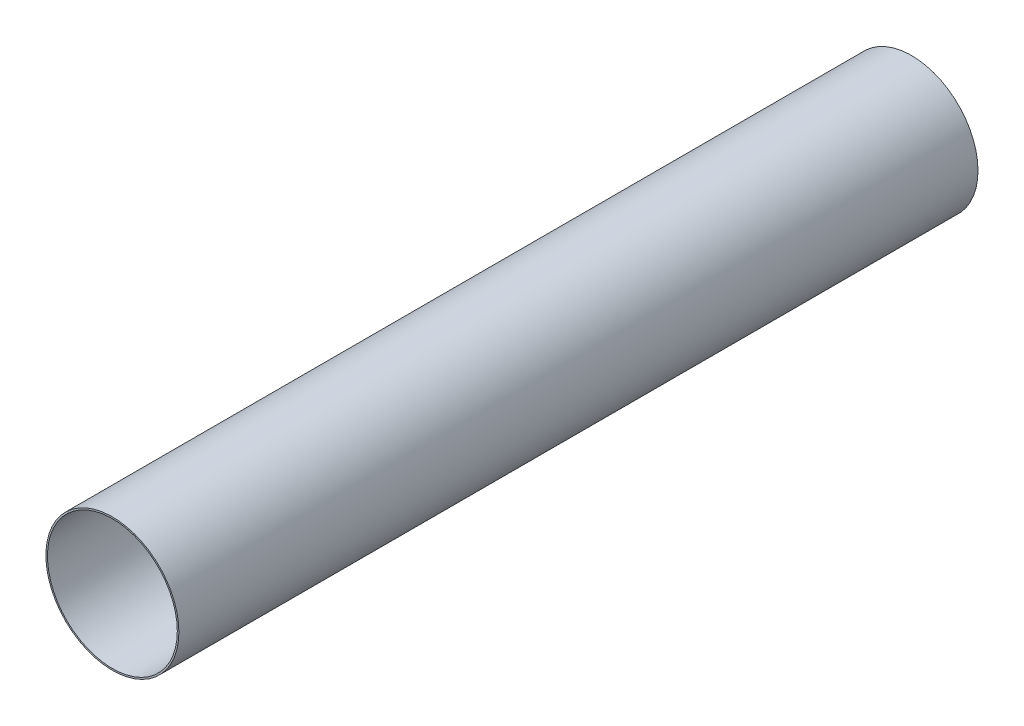
SolidWorks part; units mm, degrees
material "Thornel Mat VMA"
ref_plane "Front Plane" through (0, 0, 0) normal (0, 0, 1) x (1, 0, 0)
ref_plane "Top Plane" through (0, 0, 0) normal (0, 1, 0) x (1, 0, 0)
ref_plane "Right Plane" through (0, 0, 0) normal (1, 0, 0) x (0, 0, -1)
sketch "Sketch1" plane through (0, 0, 0) normal (0, 0, 1) x (1, 0, 0)
  circle A0 centre (0, 0) radius 84.55
  circle A1 centre (0, 0) radius 82.55
  dimension "D1" = 165.1
  dimension "D2" = 169.1
extrude "Boss-Extrude1" add sketch "Sketch1" along normal mid plane 1016
equation "\"TubeDiameter\"= 6.500in"
equation "\"D1@Sketch1\"=\"TubeDiameter\""
equation "\"D2@Sketch1\"=\"TubeDiameter\"+4mm"
